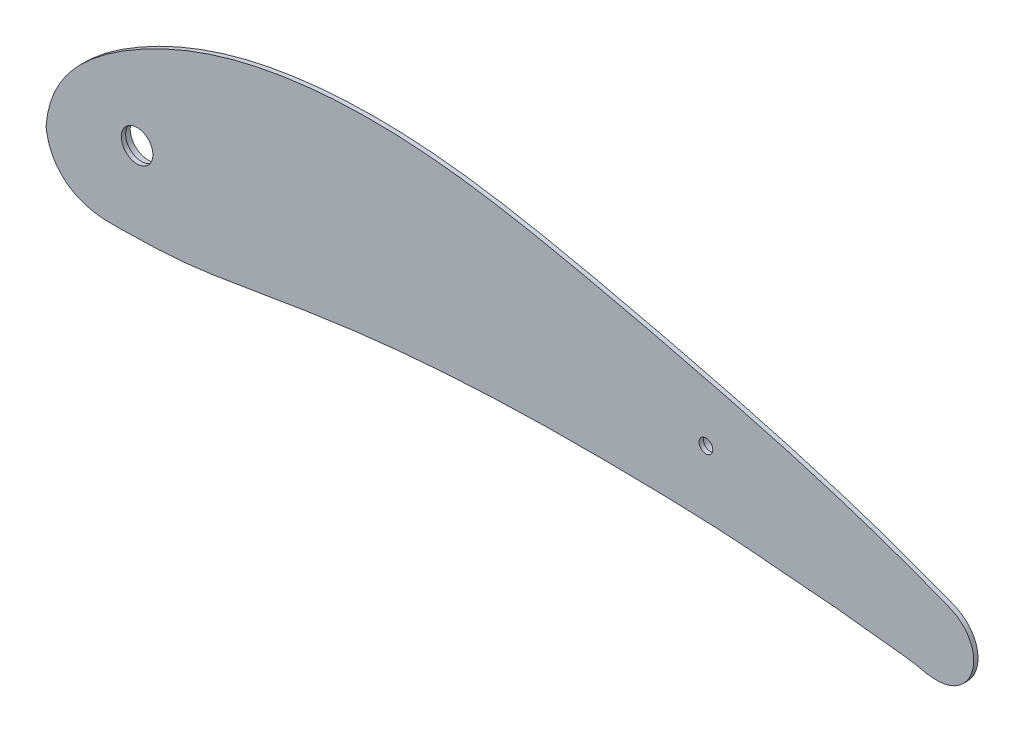
SolidWorks part; units mm, degrees
material "ABS"
ref_plane "Front Plane" through (0, 0, 0) normal (0, 0, 1) x (1, 0, 0)
ref_plane "Top Plane" through (0, 0, 0) normal (0, 1, 0) x (1, 0, 0)
ref_plane "Right Plane" through (0, 0, 0) normal (1, 0, 0) x (0, 0, -1)
sketch "Sketch1" plane through (0, 0, 0) normal (0, 0, 1) x (1, 0, 0)
  spline S0 degree 3 poles (0.0006, 0.0001) (0.8106, 7.3592) (8.6491, 17.8566) (26.2867, 29.9752) (52.1111, 42.0692) (89.5976, 49.2908) (131.4008, 47.8848) (173.2567, 40.0411) (217.9611, 29.613) (256.9521, 19.5289) (290.3598, 8.711) (301.2732, 4.3828) (314.8169, -0.5162) (309.8463, 0.0001) knots 0 0 0 0 0.060864 0.113688 0.188609 0.312909 0.448482 0.557612 0.691544 0.852438 0.929756 0.976058 1 1 1 1
  spline S1 degree 3 poles (309.8463, 0.0001) (303.9568, 1.471) (293.9895, 2.094) (276.264, 4.5144) (260.8463, 5.4274) (235.8588, 7.8703) (205.1014, 8.8381) (157.7186, 9.0307) (110.4973, 6.1815) (66.5062, -0.5867) (36.4547, -6.0985) (15.3166, -6.1891) (1.2307, -6.9241) (0.0006, 0.0001) knots 0 0 0 0 0.057787 0.095275 0.171021 0.205339 0.335319 0.464904 0.658702 0.785512 0.893517 0.943092 1 1 1 1
extrude "Boss-Extrude1" add sketch "Sketch1" along normal blind 1.5875
sketch "Sketch2" plane through (0, 0, 1.5875) normal (0, 0, 1) x (1, 0, 0)
  circle A0 centre (20.32, 10.16) radius 6.5
  circle A1 centre (227.2963, 19.0501) radius 3
  circle A2 centre (20.32, 10.16) radius 5.75
  circle A3 centre (20.32, 10.16) radius 8
  circle A4 centre (227.2963, 19.0501) radius 4.5
  circle A5 centre (227.2963, 19.0501) radius 2.5
  dimension "D2" = 13
  dimension "D3" = 6
  dimension "D6" = 20.32
  dimension "D7" = 1.5
  dimension "D8" = 11.5
  dimension "D9" = 5
  dimension "D10" = 1.5
  dimension "D1" = 82.55
  dimension "D4" = 19.05
  dimension "D5" = 10.16
extrude "Boss-Extrude2" add sketch "Sketch2" against normal blind 4 contours A4 A1 | A3 A0 region at (12.5463, 10.16, 1.5875) region at (222.9236, 19.0501, 1.5875)
extrude "Cut-Extrude1" cut sketch "Sketch2<4>" against normal blind 4 contours A5 | A2 region at (20.32, 10.16, 1.5875) region at (227.2963, 19.0501, 1.5875)
sketch "Sketch2<4>" plane through (0, 0, 1.5875) normal (0, 0, 1) x (1, 0, 0) same geometry as "Sketch2"
sketch "Sketch3" plane through (0, 0, 1.5875) normal (0, 0, 1) x (1, 0, 0)
  circle A0 centre (20.32, 10.16) radius 5.75
  circle A1 centre (227.2963, 19.0501) radius 2.5
  spline S4 degree 3 poles (-712.5026, 3937.8852) (-479.2004, 2624.6894) (-245.8981, 1311.4936) (-12.5202, -2.1281) (-12.4462, -2.5545) (-12.176, -3.8198) (-11.9472, -4.6494) (-11.3848, -6.2785) (-11.0505, -7.0797) (-10.2706, -8.6419) (-9.8324, -9.3883) (-8.861, -10.8126) (-8.3277, -11.4905) (-7.4547, -12.4548) (-7.1506, -12.7683) (-6.5217, -13.3733) (-6.1984, -13.6633) (-5.2034, -14.4972) (-4.5063, -15.0051) (-3.4124, -15.698) (-3.0397, -15.9175) (-2.2783, -16.3337) (-1.8884, -16.531) (0.0848, -17.4542) (1.7227, -17.9852) (4.2479, -18.5428) (5.101, -18.6886) (6.8269, -18.9121) (7.6891, -18.9885) (10.2729, -19.1376) (11.9923, -19.129) (14.5697, -19.0646) (15.4287, -19.0354) (17.1468, -18.9865) (18.006, -18.9648) (22.3019, -18.8623) (25.7393, -18.8009) (30.8907, -18.5548) (32.6071, -18.445) (36.0379, -18.1654) (37.7526, -17.9976) (46.3222, -17.046) (53.1404, -15.9299) (63.3607, -14.1884) (66.7665, -13.5989) (73.5825, -12.4617) (76.9921, -11.9088) (87.2279, -10.3137) (94.0606, -9.3352) (107.7529, -7.6313) (114.6131, -6.9129) (128.3595, -5.7224) (135.2455, -5.2485) (149.0401, -4.5139) (155.9486, -4.2533) (166.3263, -4.0025) (169.789, -3.9425) (176.7136, -3.8642) (187.0965, -3.8094) (197.4692, -3.9166) (211.2933, -4.1577) (218.2024, -4.3251) (232.0057, -4.8961) (238.8998, -5.3016) (249.2232, -6.1931) (252.662, -6.5269) (259.5451, -7.1075) (262.9889, -7.3618) (269.8748, -7.8975) (273.3169, -8.1788) (278.4736, -8.7044) (280.1911, -8.9011) (283.6248, -9.3158) (285.3412, -9.5311) (288.7752, -9.9413) (290.493, -10.1333) (293.9309, -10.4809) (295.6507, -10.6423) (299.0876, -11.0065) (300.8047, -11.2088) (303.3742, -11.6118) (304.2297, -11.763) (305.5105, -12.0268) (305.9371, -12.1209) (338.2653, -19.8229) (367.583, -68.4864) (653.9517, 3966.9941) knots -12.039895 -12.039895 -12.039895 -12.039895 0.003906 0.003906 0.007813 0.007813 0.015625 0.015625 0.023438 0.023438 0.03125 0.03125 0.039063 0.039063 0.042969 0.042969 0.046875 0.046875 0.054688 0.054688 0.058594 0.058594 0.0625 0.0625 0.078125 0.078125 0.085938 0.085938 0.09375 0.09375 0.109375 0.109375 0.117188 0.117188 0.125 0.125 0.15625 0.15625 0.171875 0.171875 0.1875 0.1875 0.25 0.25 0.28125 0.28125 0.3125 0.3125 0.375 0.375 0.4375 0.4375 0.5 0.5 0.5625 0.5625 0.59375 0.59375 0.625 0.6875 0.6875 0.75 0.75 0.8125 0.8125 0.84375 0.84375 0.875 0.875 0.90625 0.90625 0.921875 0.921875 0.9375 0.9375 0.953125 0.953125 0.96875 0.96875 0.984375 0.984375 0.992188 0.992188 0.996094 0.996094 1.288563 1.288563 1.288563 1.288563 only from (-12.8229, -0.4244) to (307.6407, -12.5391)
  spline S5 degree 3 poles (-122.7342, -3984.783) (246.7405, 44.2209) (275.8462, -9.8214) (309.7432, -12.7424) (310.2709, -12.7759) (311.3268, -12.8029) (311.854, -12.7961) (312.9063, -12.7287) (313.4338, -12.6676) (314.9872, -12.3972) (315.988, -12.1026) (317.4337, -11.4794) (317.9089, -11.2395) (318.8157, -10.7098) (319.6838, -10.1289) (320.4759, -9.4471) (321.2289, -8.7136) (321.5865, -8.3194) (322.5699, -7.0911) (323.1187, -6.2025) (323.7782, -4.7628) (323.9683, -4.2689) (324.2836, -3.2709) (324.4101, -2.7643) (324.6008, -1.736) (324.6652, -1.2125) (324.7285, -0.1569) (324.726, 0.8922) (324.5965, 1.9288) (324.4029, 2.9591) (324.2728, 3.4747) (323.7925, 4.9788) (323.3556, 5.9274) (322.5268, 7.2699) (322.2202, 7.7046) (321.5647, 8.5239) (321.2141, 8.9115) (320.4688, 9.6443) (320.074, 9.9894) (319.2406, 10.6374) (318.8058, 10.937) (317.4727, 11.7599) (316.5372, 12.2119) (314.6262, 13.0336) (313.6522, 13.4065) (311.697, 14.1371) (310.7161, 14.4939) (308.7579, 15.2168) (307.7794, 15.5801) (304.8459, 16.6752) (302.8934, 17.4143) (298.9854, 18.8838) (297.0281, 19.6095) (293.0959, 21.0105) (291.1228, 21.6913) (287.1674, 23.027) (285.1851, 23.6817) (279.2276, 25.616) (275.2421, 26.8663) (267.2584, 29.3011) (263.2585, 30.4844) (251.2359, 33.938) (243.1898, 36.1098) (231.0876, 39.2285) (227.0482, 40.2454) (218.9619, 42.248) (214.9155, 43.2353) (202.7668, 46.1582) (194.6542, 48.0498) (182.454, 50.7556) (178.3821, 51.6355) (170.2257, 53.3429) (166.1416, 54.1717) (157.9516, 55.7375) (151.7928, 56.8428) (145.598, 57.7968) (141.4589, 58.394) (139.384, 58.6732) (129.01, 59.9562) (120.6949, 60.6191) (108.1942, 60.9702) (104.0226, 60.98) (97.7575, 60.8192) (95.6678, 60.7364) (91.4859, 60.5096) (89.398, 60.3659) (79.0016, 59.4934) (70.7948, 58.305) (54.6421, 54.769) (46.6965, 52.4202) (37.9375, 48.979) (36.9667, 48.5856) (35.0302, 47.7767) (34.0635, 47.3607) (31.1797, 46.0826) (29.2785, 45.1906) (23.6392, 42.3949) (19.964, 40.3738) (14.5845, 37.0929) (12.8113, 35.9519) (9.3552, 33.571) (7.6711, 32.3308) (4.4084, 29.7311) (2.8297, 28.3718) (-0.2058, 25.5152) (-1.6628, 24.0183) (-3.3771, 22.0263) (-3.7146, 21.6218) (-4.3781, 20.7998) (-4.7047, 20.3815) (-5.6607, 19.1122) (-6.2653, 18.2488) (-7.9744, 15.603) (-8.9741, 13.7652) (-10.2375, 10.8836) (-10.6193, 9.9022) (-11.129, 8.3969) (-11.2886, 7.8885) (-11.5839, 6.8689) (-11.9916, 5.3328) (-12.2943, 3.7769) (-12.5275, 2.208) (-12.591, 1.6823) (-158.5954, -1324.688) (-304.5419, -2650.5316) (-450.4881, -3976.3754) knots -0.243874 -0.243874 -0.243874 -0.243874 0.003906 0.003906 0.007812 0.007812 0.011719 0.011719 0.015625 0.015625 0.023437 0.023437 0.027344 0.027344 0.03125 0.035156 0.035156 0.039062 0.039062 0.046875 0.046875 0.050781 0.050781 0.054687 0.054687 0.058594 0.058594 0.0625 0.066406 0.066406 0.070312 0.070312 0.078125 0.078125 0.082031 0.082031 0.085937 0.085937 0.089844 0.089844 0.09375 0.09375 0.101562 0.101562 0.109375 0.109375 0.117187 0.117187 0.125 0.125 0.140625 0.140625 0.15625 0.15625 0.171875 0.171875 0.1875 0.1875 0.21875 0.21875 0.25 0.25 0.3125 0.3125 0.34375 0.34375 0.375 0.375 0.4375 0.4375 0.46875 0.46875 0.5 0.5 0.53125 0.546875 0.546875 0.5625 0.5625 0.625 0.625 0.65625 0.65625 0.671875 0.671875 0.6875 0.6875 0.75 0.75 0.8125 0.8125 0.820312 0.820312 0.828125 0.828125 0.84375 0.84375 0.875 0.875 0.890625 0.890625 0.90625 0.90625 0.921875 0.921875 0.9375 0.9375 0.941406 0.941406 0.945312 0.945312 0.953125 0.953125 0.96875 0.96875 0.976562 0.976562 0.980469 0.980469 0.984375 0.992187 0.992187 0.996094 0.996094 10.829415 10.829415 10.829415 10.829415 only from (307.6407, -12.5391) to (-12.8229, -0.4244)
  spline S6 degree 3 poles (-12.8229, -0.4244) (-12.7472, -0.8503) (-12.6715, -1.2762) (-12.5202, -2.1281) (-12.4462, -2.5545) (-12.176, -3.8198) (-11.9472, -4.6494) (-11.3848, -6.2785) (-11.0505, -7.0797) (-10.2706, -8.6419) (-9.8324, -9.3883) (-8.861, -10.8126) (-8.3277, -11.4905) (-7.4547, -12.4548) (-7.1506, -12.7683) (-6.5217, -13.3733) (-6.1984, -13.6633) (-5.2034, -14.4972) (-4.5063, -15.0051) (-3.4124, -15.698) (-3.0397, -15.9175) (-2.2783, -16.3337) (-1.8884, -16.531) (0.0848, -17.4542) (1.7227, -17.9852) (4.2479, -18.5428) (5.101, -18.6886) (6.8269, -18.9121) (7.6891, -18.9885) (10.2729, -19.1376) (11.9923, -19.129) (14.5697, -19.0646) (15.4287, -19.0354) (17.1468, -18.9865) (18.006, -18.9648) (22.3019, -18.8623) (25.7393, -18.8009) (30.8907, -18.5548) (32.6071, -18.445) (36.0379, -18.1654) (37.7526, -17.9976) (46.3222, -17.046) (53.1404, -15.9299) (63.3607, -14.1884) (66.7665, -13.5989) (73.5825, -12.4617) (76.9921, -11.9088) (87.2279, -10.3137) (94.0606, -9.3352) (107.7529, -7.6313) (114.6131, -6.9129) (128.3595, -5.7224) (135.2455, -5.2485) (149.0401, -4.5139) (155.9486, -4.2533) (166.3263, -4.0025) (169.789, -3.9425) (176.7136, -3.8642) (187.0965, -3.8094) (197.4692, -3.9166) (211.2933, -4.1577) (218.2024, -4.3251) (232.0057, -4.8961) (238.8998, -5.3016) (249.2232, -6.1931) (252.662, -6.5269) (259.5451, -7.1075) (262.9889, -7.3618) (269.8748, -7.8975) (273.3169, -8.1788) (278.4736, -8.7044) (280.1911, -8.9011) (283.6248, -9.3158) (285.3412, -9.5311) (288.7752, -9.9413) (290.493, -10.1333) (293.9309, -10.4809) (295.6507, -10.6423) (299.0876, -11.0065) (300.8047, -11.2088) (303.3742, -11.6118) (304.2297, -11.763) (305.5105, -12.0268) (305.9371, -12.1209) (306.7892, -12.3239) (307.2149, -12.4328) (307.6407, -12.5391) knots 0 0 0 0 0.003906 0.003906 0.007813 0.007813 0.015625 0.015625 0.023438 0.023438 0.03125 0.03125 0.039063 0.039063 0.042969 0.042969 0.046875 0.046875 0.054688 0.054688 0.058594 0.058594 0.0625 0.0625 0.078125 0.078125 0.085938 0.085938 0.09375 0.09375 0.109375 0.109375 0.117188 0.117188 0.125 0.125 0.15625 0.15625 0.171875 0.171875 0.1875 0.1875 0.25 0.25 0.28125 0.28125 0.3125 0.3125 0.375 0.375 0.4375 0.4375 0.5 0.5 0.5625 0.5625 0.59375 0.59375 0.625 0.6875 0.6875 0.75 0.75 0.8125 0.8125 0.84375 0.84375 0.875 0.875 0.90625 0.90625 0.921875 0.921875 0.9375 0.9375 0.953125 0.953125 0.96875 0.96875 0.984375 0.984375 0.992188 0.992188 0.996094 0.996094 1 1 1 1
  spline S7 degree 3 poles (307.6407, -12.5391) (308.166, -12.5937) (308.691, -12.6517) (309.7432, -12.7424) (310.2709, -12.7759) (311.3268, -12.8029) (311.854, -12.7961) (312.9063, -12.7287) (313.4338, -12.6676) (314.9872, -12.3972) (315.988, -12.1026) (317.4337, -11.4794) (317.9089, -11.2395) (318.8157, -10.7098) (319.6838, -10.1289) (320.4759, -9.4471) (321.2289, -8.7136) (321.5865, -8.3194) (322.5699, -7.0911) (323.1187, -6.2025) (323.7782, -4.7628) (323.9683, -4.2689) (324.2836, -3.2709) (324.4101, -2.7643) (324.6008, -1.736) (324.6652, -1.2125) (324.7285, -0.1569) (324.726, 0.8922) (324.5965, 1.9288) (324.4029, 2.9591) (324.2728, 3.4747) (323.7925, 4.9788) (323.3556, 5.9274) (322.5268, 7.2699) (322.2202, 7.7046) (321.5647, 8.5239) (321.2141, 8.9115) (320.4688, 9.6443) (320.074, 9.9894) (319.2406, 10.6374) (318.8058, 10.937) (317.4727, 11.7599) (316.5372, 12.2119) (314.6262, 13.0336) (313.6522, 13.4065) (311.697, 14.1371) (310.7161, 14.4939) (308.7579, 15.2168) (307.7794, 15.5801) (304.8459, 16.6752) (302.8934, 17.4143) (298.9854, 18.8838) (297.0281, 19.6095) (293.0959, 21.0105) (291.1228, 21.6913) (287.1674, 23.027) (285.1851, 23.6817) (279.2276, 25.616) (275.2421, 26.8663) (267.2584, 29.3011) (263.2585, 30.4844) (251.2359, 33.938) (243.1898, 36.1098) (231.0876, 39.2285) (227.0482, 40.2454) (218.9619, 42.248) (214.9155, 43.2353) (202.7668, 46.1582) (194.6542, 48.0498) (182.454, 50.7556) (178.3821, 51.6355) (170.2257, 53.3429) (166.1416, 54.1717) (157.9516, 55.7375) (151.7928, 56.8428) (145.598, 57.7968) (141.4589, 58.394) (139.384, 58.6732) (129.01, 59.9562) (120.6949, 60.6191) (108.1942, 60.9702) (104.0226, 60.98) (97.7575, 60.8192) (95.6678, 60.7364) (91.4859, 60.5096) (89.398, 60.3659) (79.0016, 59.4934) (70.7948, 58.305) (54.6421, 54.769) (46.6965, 52.4202) (37.9375, 48.979) (36.9667, 48.5856) (35.0302, 47.7767) (34.0635, 47.3607) (31.1797, 46.0826) (29.2785, 45.1906) (23.6392, 42.3949) (19.964, 40.3738) (14.5845, 37.0929) (12.8113, 35.9519) (9.3552, 33.571) (7.6711, 32.3308) (4.4084, 29.7311) (2.8297, 28.3718) (-0.2058, 25.5152) (-1.6628, 24.0183) (-3.3771, 22.0263) (-3.7146, 21.6218) (-4.3781, 20.7998) (-4.7047, 20.3815) (-5.6607, 19.1122) (-6.2653, 18.2488) (-7.9744, 15.603) (-8.9741, 13.7652) (-10.2375, 10.8836) (-10.6193, 9.9022) (-11.129, 8.3969) (-11.2886, 7.8885) (-11.5839, 6.8689) (-11.9916, 5.3328) (-12.2943, 3.7769) (-12.5275, 2.208) (-12.591, 1.6823) (-12.7069, 0.629) (-12.7649, 0.1023) (-12.8229, -0.4244) knots 0 0 0 0 0.003906 0.003906 0.007812 0.007812 0.011719 0.011719 0.015625 0.015625 0.023437 0.023437 0.027344 0.027344 0.03125 0.035156 0.035156 0.039062 0.039062 0.046875 0.046875 0.050781 0.050781 0.054687 0.054687 0.058594 0.058594 0.0625 0.066406 0.066406 0.070312 0.070312 0.078125 0.078125 0.082031 0.082031 0.085937 0.085937 0.089844 0.089844 0.09375 0.09375 0.101562 0.101562 0.109375 0.109375 0.117187 0.117187 0.125 0.125 0.140625 0.140625 0.15625 0.15625 0.171875 0.171875 0.1875 0.1875 0.21875 0.21875 0.25 0.25 0.3125 0.3125 0.34375 0.34375 0.375 0.375 0.4375 0.4375 0.46875 0.46875 0.5 0.5 0.53125 0.546875 0.546875 0.5625 0.5625 0.625 0.625 0.65625 0.65625 0.671875 0.671875 0.6875 0.6875 0.75 0.75 0.8125 0.8125 0.820312 0.820312 0.828125 0.828125 0.84375 0.84375 0.875 0.875 0.890625 0.890625 0.90625 0.90625 0.921875 0.921875 0.9375 0.9375 0.941406 0.941406 0.945312 0.945312 0.953125 0.953125 0.96875 0.96875 0.976562 0.976562 0.980469 0.980469 0.984375 0.992187 0.992187 0.996094 0.996094 1 1 1 1
  dimension "D1" = 12.7
extrude "Boss-Extrude3" add sketch "Sketch3" against normal up to surface (1.5875 mm away) up to face at (12.32, 10.16, 0)
